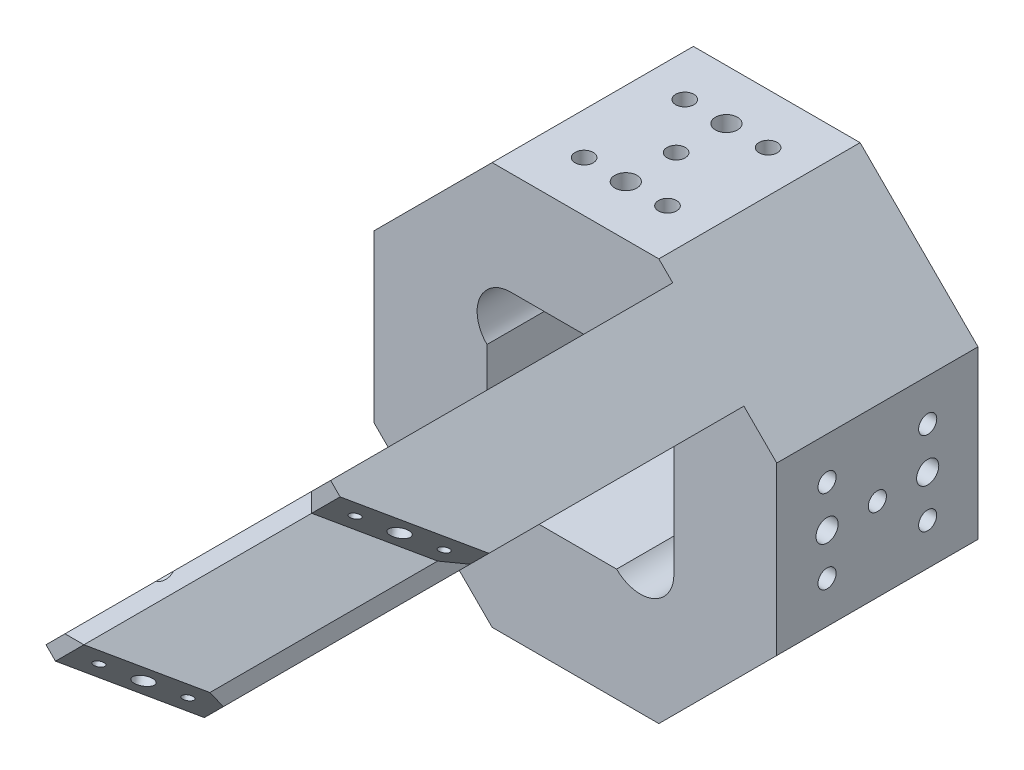
SolidWorks part; units mm, degrees
ref_plane "Front Plane" through (0, 0, 0) normal (0, 0, 1) x (1, 0, 0)
ref_plane "Top Plane" through (0, 0, 0) normal (0, 1, 0) x (1, 0, 0)
ref_plane "Right Plane" through (0, 0, 0) normal (1, 0, 0) x (0, 0, -1)
sketch "Sketch1" plane through (0, 0, 0) normal (0, 0, 1) x (1, 0, 0)
  line L0 (-12.4264, -30) -> (12.4264, -30)
  line L1 (30, -12.4264) -> (30, 12.4264)
  line L2 (30, 12.4264) -> (12.4264, 30)
  line L3 (12.4264, 30) -> (-12.4264, 30)
  line L4 (-12.4264, 30) -> (-30, 12.4264)
  line L5 (-30, 12.4264) -> (-30, -12.4264)
  line L6 (-30, -12.4264) -> (-12.4264, -30)
  line L7 (12.4264, -30) -> (30, -12.4264)
  line L9 (-13.2, 13.2) -> (13.2, 13.2)
  line L10 (-13.2, 13.2) -> (-13.2, -13.2)
  line L11 (-13.2, -13.2) -> (13.2, -13.2)
  line L12 (13.2, 13.2) -> (13.2, -13.2)
  line L13 (-13.2, 13.2) -> (13.2, -13.2) construction
  line L14 (-13.2, -13.2) -> (13.2, 13.2) construction
  circle A0 centre (0, 0) radius 30 construction
  dimension "D1" = 60
  dimension "D2" = 26.4
extrude "Boss-Extrude1" add sketch "Sketch1" along normal blind 30
sketch "Sketch2" plane through (0, 0, 30) normal (0, 0, 1) x (1, 0, 0)
  line L0 (-12.4264, 30) -> (-30, 12.4264) construction
  line L1 (-30, 12.4264) -> (-25.0503, 7.4767) construction
  line L2 (-25.0503, 7.4767) -> (-7.4767, 25.0503) construction
  line L3 (-7.4767, 25.0503) -> (-12.4264, 30) construction
  line L4 (12.4264, -30) -> (30, -12.4264) construction
  line L5 (30, -12.4264) -> (25.0503, -7.4767) construction
  line L6 (25.0503, -7.4767) -> (7.4767, -25.0503) construction
  line L7 (7.4767, -25.0503) -> (12.4264, -30) construction
  line L8 (14.4957, 27.9307) -> (25.1023, 17.3241)
  line L9 (25.1023, 17.3241) -> (20.8597, 13.0815)
  line L10 (20.8597, 13.0815) -> (10.253, 23.6881)
  line L11 (10.253, 23.6881) -> (14.4957, 27.9307)
  line L12 (-27.9307, -14.4957) -> (-17.3241, -25.1023)
  line L13 (-17.3241, -25.1023) -> (-13.0815, -20.8597)
  line L14 (-13.0815, -20.8597) -> (-23.6881, -10.253)
  line L15 (-23.6881, -10.253) -> (-27.9307, -14.4957)
  line L16 (30, 12.4264) -> (12.4264, 30) construction
  line L17 (21.2132, 21.2132) -> (13.2, 13.2) construction
  line L18 (-30, -12.4264) -> (-12.4264, -30) construction
  dimension "D1" = 7
  dimension "D2" = 6
  dimension "D3" = 5.5
  dimension "D4" = 9.5
extrude "Boss-Extrude2" add sketch "Sketch2" along normal blind 53
sketch "Sketch3" plane through (21.2132, 21.2132, 0) normal (0.7071, 0.7071, 0) x (0, 0, -1)
  line L3 (-83, 9.5) -> (-83, -5.5)
  line L4 (-83, 9.5) -> (-68, -5.5)
  line L5 (-83, -5.5) -> (-30, -5.5) construction
  line L6 (-68, -5.5) -> (-83, -5.5)
  dimension "D1" = 45
extrude "Cut-Extrude1" cut sketch "Sketch3" against normal through all
ref_plane "Plane1" through (26.7362, -26.7362, 37.8107) normal (0.5, -0.5, 0.7071) x (0.866, 0.2887, -0.4082)
ref_axis "Axis1" through (0, 0, 0) along (0, 0, -1)
ref_point "Point1"
hole_wizard "#6-32 Tapped Hole1" positions "Sketch14" profile "Sketch15" tap size "#6-32" standard "ANSI Inch" end condition through all
sketch "Sketch14" plane through (26.7362, -26.7362, 37.8107) normal (0.5, -0.5, 0.7071) x (0.866, 0.2887, -0.4082)
  line L7 (-52.9177, 28.0715) -> (-8.8269, 59.2484) construction
  line L9 (-57.3589, 39.5485) -> (-62.2579, 36.0844) construction
  line L10 (-8.8269, 59.2484) -> (-3.4701, 51.6728) construction
  line L11 (-5.9196, 49.9408) -> (-1.0206, 53.4049) construction
  point P0 (-8.8269, 59.2484)
  point P19 (-52.9177, 28.0715)
sketch "Sketch15" plane through (19.0919, 19.0919, 75.6213) normal (0.7071, 0.7071, 0) x (0.5, -0.5, -0.7071)
  line L0 (0, 0) -> (0, 83.4723)
  line L1 (0, 83.4723) -> (1.3525, 83.4723)
  line L2 (1.3525, 83.4723) -> (1.3525, 0)
  line L5 (1.3525, 0) -> (0, 0)
  line L11 (0, -6.35) -> (0, 107.95) construction
  dimension "Thru Tap Drill Dia." = 2.7051
  dimension "Thru Tap Drill Depth" = 83.4723
cosmetic thread "Hole Thread7" parameters "D2"=3.5052
cosmetic thread "Hole Thread8" parameters "D2"=3.5052
hole_wizard "#1-72 Tapped Hole1" positions "Sketch18" profile "Sketch19" tap size "#1-72" standard "ANSI Inch" end condition through all
sketch "Sketch18" plane through (25.9862, -25.9862, 36.75) normal (0.5, -0.5, 0.7071) x (0.866, 0.2887, -0.4082)
  line L0 (-8.8269, 59.2484) -> (-12.0023, 63.7392) construction
  line L2 (-8.8269, 59.2484) -> (-5.6514, 54.7577) construction
  line L13 (-18.167, 67.2613) -> (-5.9196, 49.9408) construction
  line L14 (-5.9196, 49.9408) -> (-18.167, 67.2613) construction
  line L16 (-5.9196, 49.9408) -> (-1.0206, 53.4049) construction
  line L17 (-52.9177, 28.0715) -> (-56.0931, 32.5623) construction
  line L19 (-52.9177, 28.0715) -> (-49.7423, 23.5808) construction
  line L21 (-50.0104, 18.7639) -> (-62.2579, 36.0844) construction
  point P0 (-12.0023, 63.7392)
  point P2 (-5.6514, 54.7577)
  point P4 (-56.0931, 32.5623)
  point P6 (-49.7423, 23.5808)
  dimension "D1" = 11
  dimension "D2" = 11
sketch "Sketch19" plane through (15.5919, 22.5919, 78.4497) normal (0.7071, 0.7071, 0) x (0.5, -0.5, -0.7071)
  line L0 (0, 0) -> (0, 81.9723)
  line L1 (0, 81.9723) -> (0.7556, 81.9723)
  line L2 (0.7556, 81.9723) -> (0.7556, 0)
  line L5 (0.7556, 0) -> (0, 0)
  line L11 (0, -6.35) -> (0, 107.95) construction
  dimension "Thru Tap Drill Dia." = 1.5113
  dimension "Thru Tap Drill Depth" = 81.9723
cosmetic thread "Hole Thread9" parameters "D2"=1.8542
cosmetic thread "Hole Thread10" parameters "D2"=1.8542
cosmetic thread "Hole Thread11" parameters "D2"=1.8542
cosmetic thread "Hole Thread12" parameters "D2"=1.8542
chamfer "Chamfer1" distance 2 angle 45 4 edges at (10.253, 23.6881, 56.5) (20.8597, 13.0815, 49) (-23.6881, -10.253, 56.5) (-13.0815, -20.8597, 49)
hole_wizard "M4x0.7 Tapped Hole1" positions "Sketch4" profile "Sketch6" tap size "M4x0.7" standard "ANSI Metric"
sketch "Sketch4" plane through (-30, 0, 0) normal (-1, 0, 0) x (0, 0, 1)
  line L3 (0, 0) -> (7.5, 0) construction
  line L4 (0, 12.4264) -> (0, -12.4264) construction
  line L5 (7.5, 0) -> (15, 0) construction
  line L6 (15, 0) -> (22.5, 0) construction
  line L7 (22.5, 0) -> (30, 0) construction
  line L8 (30, 12.4264) -> (30, -12.4264) construction
  point P0 (7.5, 0)
  point P2 (22.5, 0)
sketch "Sketch6" plane through (-30, 0, 7.5) normal (0, 1, 0) x (0, 0, 1)
  line L0 (0, 0) -> (0, 11.0914)
  line L1 (0, 11.0914) -> (1.65, 10.1)
  line L2 (1.65, 10.1) -> (1.65, 0)
  line L5 (1.65, 0) -> (0, 0)
  line L10 (0, 11.0914) -> (-1.65, 10.1) construction
  line L11 (0, -6.35) -> (0, 107.95) construction
  dimension "Tap Drill Dia." = 3.3
  dimension "Tap Drill Depth" = 10.1
  dimension "Drill Angle" = 118
cosmetic thread "Hole Thread1" parameters "D1"=8, "D2"=4
cosmetic thread "Hole Thread2" parameters "D1"=8, "D2"=4
hole_wizard "M4x0.7 Tapped Hole2" positions "Sketch7" profile "Sketch8" tap size "M4x0.7" standard "ANSI Metric"
sketch "Sketch7" plane through (0, -30, 0) normal (0, -1, 0) x (-1, 0, 0)
  line L0 (0, 0) -> (0, -7.5) construction
  line L1 (12.4264, 0) -> (-12.4264, 0) construction
  line L2 (0, -7.5) -> (0, -15) construction
  line L3 (0, -15) -> (0, -22.5) construction
  line L4 (0, -22.5) -> (0, -30) construction
  line L5 (12.4264, -30) -> (-12.4264, -30) construction
  point P2 (0, -7.5)
  point P9 (0, -22.5)
sketch "Sketch8" plane through (0, -30, 22.5) normal (1, 0, 0) x (0, 0, -1)
  line L0 (0, 0) -> (0, 11.0914)
  line L1 (0, 11.0914) -> (1.65, 10.1)
  line L2 (1.65, 10.1) -> (1.65, 0)
  line L5 (1.65, 0) -> (0, 0)
  line L10 (0, 11.0914) -> (-1.65, 10.1) construction
  line L11 (0, -6.35) -> (0, 107.95) construction
  dimension "Tap Drill Dia." = 3.3
  dimension "Tap Drill Depth" = 10.1
  dimension "Drill Angle" = 118
cosmetic thread "Hole Thread3" parameters "D1"=8, "D2"=4
cosmetic thread "Hole Thread4" parameters "D1"=8, "D2"=4
hole_wizard "M4x0.7 Tapped Hole3" positions "Sketch9" profile "Sketch10" tap size "M4x0.7" standard "ANSI Metric"
sketch "Sketch9" plane through (21.2132, -21.2132, 0) normal (0.7071, -0.7071, 0) x (0, 0, -1)
  line L0 (0, 0) -> (-7.5, 0) construction
  line L1 (-7.5, 0) -> (-15, 0) construction
  line L2 (-15, 0) -> (-22.5, 0) construction
  line L3 (-22.5, 0) -> (-30, 0) construction
  point P1 (-7.5, 0)
  point P6 (-22.5, 0)
sketch "Sketch10" plane through (21.2132, -21.2132, 22.5) normal (0, 0, 1) x (0.7071, 0.7071, 0)
  line L0 (0, 0) -> (0, 11.0914)
  line L1 (0, 11.0914) -> (1.65, 10.1)
  line L2 (1.65, 10.1) -> (1.65, 0)
  line L5 (1.65, 0) -> (0, 0)
  line L10 (0, 11.0914) -> (-1.65, 10.1) construction
  line L11 (0, -6.35) -> (0, 107.95) construction
  dimension "Tap Drill Dia." = 3.3
  dimension "Tap Drill Depth" = 10.1
  dimension "Drill Angle" = 118
cosmetic thread "Hole Thread5" parameters "D1"=8, "D2"=4
cosmetic thread "Hole Thread6" parameters "D1"=8, "D2"=4
sketch "Sketch20" plane through (21.2132, 21.2132, 0) normal (0.7071, 0.7071, 0) x (0, 0, -1)
  line L0 (-83, 9.5) -> (-81, 9.5)
  line L1 (-83, 9.5) -> (-30, 9.5) construction
  line L2 (-81, 9.5) -> (-81, 7.5)
  line L3 (-68, -5.5) -> (-83, 9.5) construction
  line L4 (-81, 7.5) -> (-83, 9.5)
  dimension "D1" = 2
extrude "Cut-Extrude2" cut sketch "Sketch20" against normal through all
hole_wizard "M4x0.7 Tapped Hole4" positions "Sketch21" profile "Sketch23" tap size "M4x0.7" standard "ANSI Metric"
sketch "Sketch21" plane through (0, 30, 0) normal (0, 1, 0) x (1, 0, 0)
  line L0 (0, 0) -> (0, -7.5) construction
  line L1 (0, -7.5) -> (0, -15) construction
  line L2 (0, 0) -> (0, 28.0014) construction
  line L3 (0, -15) -> (0, -22.5) construction
  line L4 (0, -22.5) -> (0, -30) construction
  line L5 (12.4264, -30) -> (-12.4264, -30) construction
  point P0 (0, -7.5)
  point P2 (0, -22.5)
sketch "Sketch23" plane through (0, 30, 7.5) normal (1, 0, 0) x (0, 0, 1)
  line L0 (0, 0) -> (0, 11.0914)
  line L1 (0, 11.0914) -> (1.65, 10.1)
  line L2 (1.65, 10.1) -> (1.65, 0)
  line L5 (1.65, 0) -> (0, 0)
  line L10 (0, 11.0914) -> (-1.65, 10.1) construction
  line L11 (0, -6.35) -> (0, 107.95) construction
  dimension "Tap Drill Dia." = 3.3
  dimension "Tap Drill Depth" = 10.1
  dimension "Drill Angle" = 118
cosmetic thread "Hole Thread13" parameters "D1"=8, "D2"=4
cosmetic thread "Hole Thread14" parameters "D1"=8, "D2"=4
sketch "Sketch24" plane through (0, 0, 0) normal (0, 0, -1) x (-1, 0, 0)
  line L0 (-13.2, 13.2) -> (13.2, -13.2) construction
  line L1 (13.2, 13.2) -> (-13.2, -13.2) construction
  circle A0 centre (-9.6645, 9.6645) radius 5
  circle A1 centre (9.6645, 9.6645) radius 5
  circle A2 centre (9.6645, -9.6645) radius 5
  circle A3 centre (-9.6645, -9.6645) radius 5
  dimension "D1" = 10
extrude "Cut-Extrude3" cut sketch "Sketch24" against normal through all
sketch "Sketch25" plane through (0, 0, 0) normal (0, 0, -1) x (-1, 0, 0)
  line L0 (-13.2, -6.1289) -> (-13.2, 6.1289) construction
  line L1 (9.6645, 14.6645) -> (-9.6645, 14.6645)
  line L2 (9.6645, 14.6645) -> (9.6645, 13.2)
  line L3 (9.6645, 13.2) -> (-9.6645, 13.2)
  line L4 (-9.6645, 14.6645) -> (-9.6645, 13.2)
  line L5 (-14.6645, -9.6645) -> (-13.2, -9.6645)
  line L6 (-14.6645, -9.6645) -> (-14.6645, 9.6645)
  line L7 (-14.6645, 9.6645) -> (-13.2, 9.6645)
  line L8 (-13.2, -9.6645) -> (-13.2, 9.6645)
  line L9 (-6.1289, 13.2) -> (6.1289, 13.2) construction
  arc A0 (13.2, 6.1289) -> (6.1289, 13.2) centre (9.6645, 9.6645) ccw construction
  arc A1 (-13.2, -6.1289) -> (-6.1289, -13.2) centre (-9.6645, -9.6645) ccw construction
  arc A2 (-6.1289, 13.2) -> (-13.2, 6.1289) centre (-9.6645, 9.6645) ccw construction
  point P19 (-9.6645, 9.6645)
  point P22 (9.6645, 9.6645)
  point P25 (-9.6645, -9.6645)
extrude "Cut-Extrude4" cut sketch "Sketch25" against normal through all
hole_wizard "#6-32 Tapped Hole2" positions "Sketch26" profile "Sketch27" tap size "#6-32" standard "ANSI Inch" end condition up to next
sketch "Sketch26" plane through (0, 30, 0) normal (0, 1, 0) x (1, 0, 0)
  line L2 (12.4264, 0) -> (6.2132, -7.5) construction
  line L3 (6.2132, -7.5) -> (0, -15) construction
  line L4 (0, -15) -> (-6.2132, -22.5) construction
  line L5 (-6.2132, -22.5) -> (-12.4264, -30) construction
  line L7 (-12.4264, 0) -> (-6.2132, -7.5) construction
  line L8 (-6.2132, -7.5) -> (0, -15) construction
  line L9 (0, -15) -> (6.2132, -22.5) construction
  line L10 (6.2132, -22.5) -> (12.4264, -30) construction
  point P0 (0, -15)
  point P2 (-6.2132, -7.5)
  point P4 (6.2132, -7.5)
  point P6 (-6.2132, -22.5)
  point P8 (6.2132, -22.5)
cosmetic thread "Hole Thread15" parameters "D2"=3.5052
cosmetic thread "Hole Thread16" parameters "D2"=3.5052
cosmetic thread "Hole Thread17" parameters "D2"=3.5052
cosmetic thread "Hole Thread18" parameters "D2"=3.5052
cosmetic thread "Hole Thread19" parameters "D2"=3.5052
sketch "Sketch27" plane through (0, 30, 15) normal (1, 0, 0) x (0, 0, 1)
  line L0 (0, 0) -> (0, 15.3355)
  line L1 (0, 15.3355) -> (1.3525, 15.3355)
  line L2 (1.3525, 15.3355) -> (1.3525, 0)
  line L5 (1.3525, 0) -> (0, 0)
  line L11 (0, -6.35) -> (0, 107.95) construction
  dimension "Thru Tap Drill Dia." = 2.7051
  dimension "Thru Tap Drill Depth" = 15.3355
hole_wizard "#6-32 Tapped Hole3" positions "Sketch28" profile "Sketch29" tap size "#6-32" standard "ANSI Inch" end condition up to next
sketch "Sketch28" plane through (30, 0, 0) normal (1, 0, 0) x (0, 0, -1)
  line L0 (0, 12.4264) -> (-7.5, 6.2132) construction
  line L1 (-7.5, 6.2132) -> (-15, 0) construction
  line L2 (-15, 0) -> (-22.5, -6.2132) construction
  line L3 (-22.5, -6.2132) -> (-30, -12.4264) construction
  line L5 (-30, 12.4264) -> (-22.5, 6.2132) construction
  line L6 (-22.5, 6.2132) -> (-15, 0) construction
  line L7 (-15, 0) -> (-7.5, -6.2132) construction
  line L8 (-7.5, -6.2132) -> (0, -12.4264) construction
  point P0 (-15, 0)
  point P2 (-7.5, 6.2132)
  point P4 (-22.5, -6.2132)
  point P6 (-22.5, 6.2132)
  point P8 (-7.5, -6.2132)
sketch "Sketch29" plane through (30, 0, 15) normal (0, 1, 0) x (0, 0, -1)
  line L0 (0, 0) -> (0, 15.3355)
  line L1 (0, 15.3355) -> (1.3525, 15.3355)
  line L2 (1.3525, 15.3355) -> (1.3525, 0)
  line L5 (1.3525, 0) -> (0, 0)
  line L11 (0, -6.35) -> (0, 107.95) construction
  dimension "Thru Tap Drill Dia." = 2.7051
  dimension "Thru Tap Drill Depth" = 15.3355
cosmetic thread "Hole Thread20" parameters "D2"=3.5052
cosmetic thread "Hole Thread21" parameters "D2"=3.5052
cosmetic thread "Hole Thread22" parameters "D2"=3.5052
cosmetic thread "Hole Thread23" parameters "D2"=3.5052
cosmetic thread "Hole Thread24" parameters "D2"=3.5052
hole_wizard "M4x0.7 Tapped Hole6" positions "Sketch30" profile "Sketch32" tap size "M4x0.7" standard "ANSI Metric"
sketch "Sketch30" plane through (30, 0, 0) normal (1, 0, 0) x (0, 0, -1)
  line L0 (0, 0) -> (-7.5, 0) construction
  line L1 (-7.5, 0) -> (-15, 0) construction
  line L2 (0, 0) -> (28.0014, 0) construction
  line L3 (-15, 0) -> (-22.5, 0) construction
  line L4 (-22.5, 0) -> (-30, 0) construction
  line L5 (-30, -12.4264) -> (-30, 12.4264) construction
  point P0 (-22.5, 0)
  point P2 (-7.5, 0)
sketch "Sketch32" plane through (30, 0, 22.5) normal (0, 1, 0) x (0, 0, -1)
  line L0 (0, 0) -> (0, 11.0914)
  line L1 (0, 11.0914) -> (1.65, 10.1)
  line L2 (1.65, 10.1) -> (1.65, 0)
  line L5 (1.65, 0) -> (0, 0)
  line L10 (0, 11.0914) -> (-1.65, 10.1) construction
  line L11 (0, -6.35) -> (0, 107.95) construction
  dimension "Tap Drill Dia." = 3.3
  dimension "Tap Drill Depth" = 10.1
  dimension "Drill Angle" = 118
cosmetic thread "Hole Thread25" parameters "D1"=8, "D2"=4
cosmetic thread "Hole Thread26" parameters "D1"=8, "D2"=4
